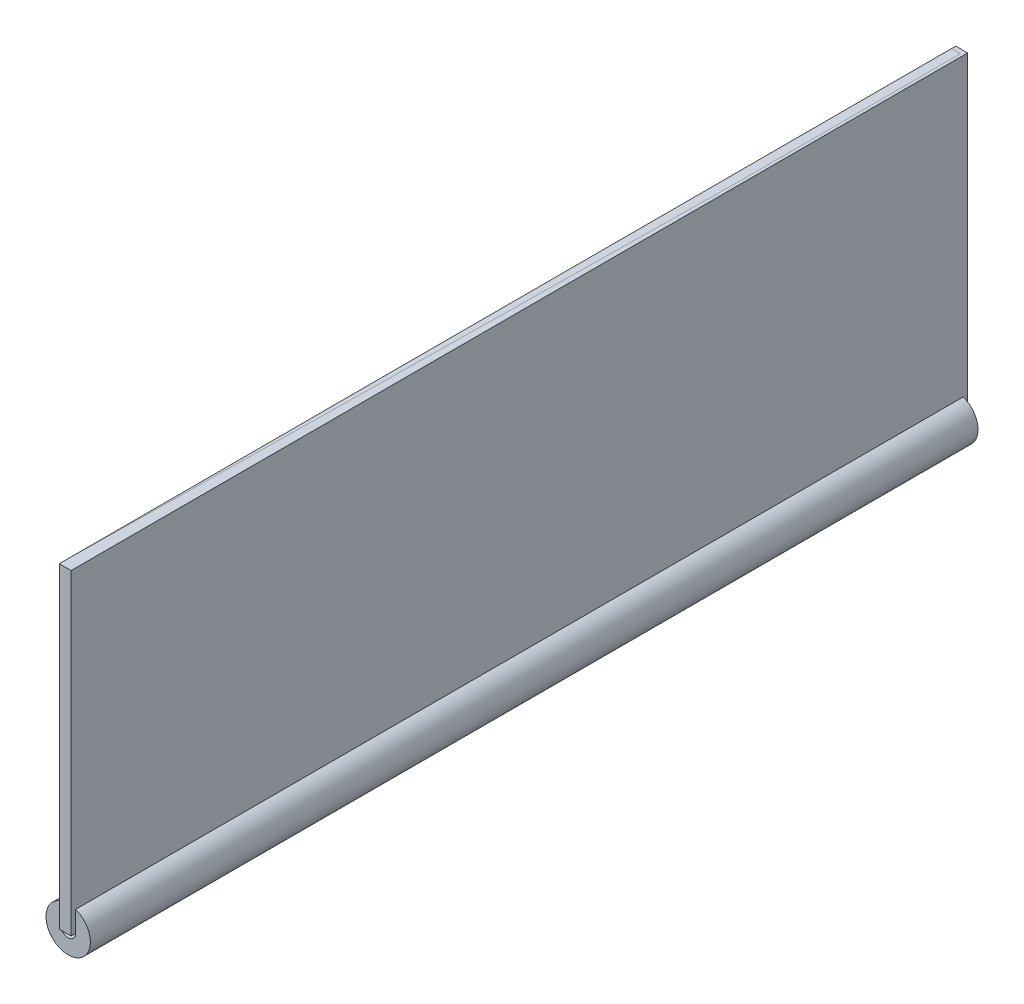
SolidWorks part; units mm, degrees
note: '?' marks a value the reader was unsure of.
other "COLL.BOX-Estrusione-Estrusione5"
ref_plane "Piano frontale" through (0, 0, 0) normal (0, 0, 1) x (1, 0, 0)
ref_plane "Piano superiore" through (0, 0, 0) normal (0, 1, 0) x (1, 0, 0)
ref_plane "Piano destro" through (0, 0, 0) normal (1, 0, 0) x (0, 0, -1)
sketch "Schizzo7" plane through (0, 0, 0) normal (1, 0, 0) x (0, 0, -1)
  line L1 (150, -53.5) -> (-150, -53.5)
  line L2 (150, -53.5) -> (150, 53.5)
  line L3 (150, 53.5) -> (-150, 53.5)
  line L4 (-150, -53.5) -> (-150, 53.5)
  line L5 (150, -53.5) -> (-150, 53.5) construction
  line L6 (150, 53.5) -> (-150, -53.5) construction
  point P0 (0, 0)
  dimension "D1" = 300
  dimension "D2" = 107
extrude "Estrusione-Estrusione4" add sketch "Schizzo7" along normal blind 3
sketch "Schizzo8" plane through (0, 0, 150) normal (0, 0, 1) x (1, 0, 0)
  line L0 (3, -53.5) -> (0, -53.5) construction
  circle A0 centre (1.5, -53.5) radius 7.5
  dimension "D1" = 15
sweep "Sweep2" add profiles "Schizzo8" path edge at (3, -53.5, 0)
sketch "Schizzo9" plane through (0, 0, 150) normal (0, 0, 1) x (1, 0, 0)
  circle A0 centre (1.5, -53.5) radius 2.5
  dimension "D1" = 5
extrude "Taglio-Estrusione1" cut sketch "Schizzo9" against normal through all
ref_axis "Assi2" through (1.5, -53.5, -150) along (0, 0, 1)?
sketch "Schizzo11" plane through (0, 0, 0) normal (1, 0, 0) x (0, 0, -1)
  line L1 (-151.5, 53.5) -> (151.5, 53.5)
  line L2 (-151.5, 53.5) -> (-151.5, -53.5)
  line L3 (-151.5, -53.5) -> (151.5, -53.5)
  line L4 (151.5, 53.5) -> (151.5, -53.5)
  line L5 (-151.5, 53.5) -> (151.5, -53.5) construction
  line L6 (-151.5, -53.5) -> (151.5, 53.5) construction
  point P0 (0, 0)
  dimension "D1" = 303
  dimension "D2" = 107
extrude "Estrusione-Estrusione5" add sketch "Schizzo11" along normal blind 4 separate body
